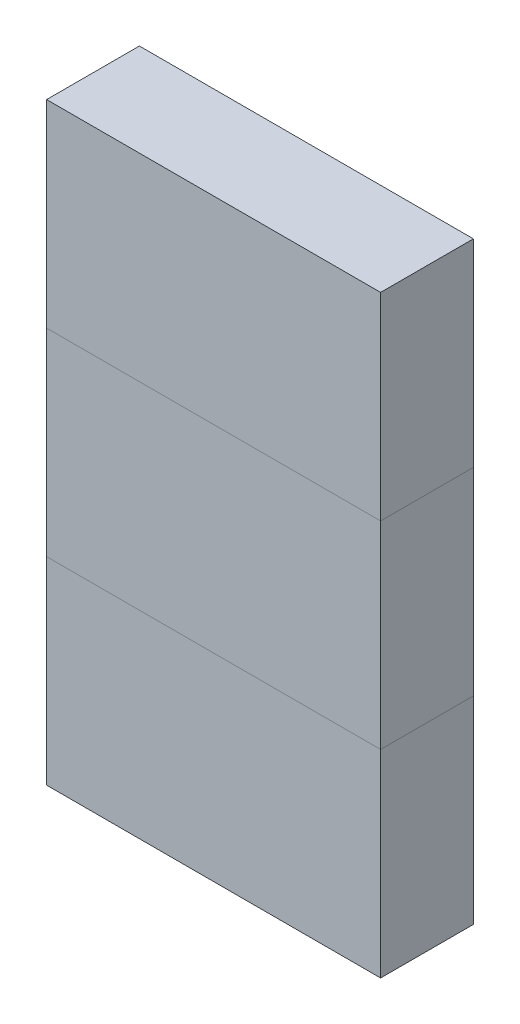
SolidWorks part; units mm, degrees
note: The reader was unsure of these and kept them because the rebuilt part matched: shared geometry of "Sketch2<3>", "Sketch2<4>".
other "middle block"
other "bottom block"
other "top block"
material "ABS"
ref_plane "Front" through (0, 0, 0) normal (0, 0, 1) x (1, 0, 0)
ref_plane "Top" through (0, 0, 0) normal (0, 1, 0) x (1, 0, 0)
ref_plane "Right" through (0, 0, 0) normal (1, 0, 0) x (0, 0, -1)
sketch "Sketch1" plane through (0, 0, 0) normal (0, 1, 0) x (1, 0, 0)
  line L1 (-28.575, 7.9375) -> (28.575, 7.9375)
  line L2 (-28.575, 7.9375) -> (-28.575, -7.9375)
  line L3 (-28.575, -7.9375) -> (28.575, -7.9375)
  line L4 (28.575, 7.9375) -> (28.575, -7.9375)
  line L5 (-28.575, 7.9375) -> (28.575, -7.9375) construction
  line L6 (-28.575, -7.9375) -> (28.575, 7.9375) construction
  point P0 (0, 0)
  dimension "D1" = 15.875
  dimension "D2" = 57.15
extrude "Boss-Extrude1" add sketch "Sketch1" along normal mid plane 101.6
sketch "Sketch2" plane through (0, 0, 0) normal (0, 1, 0) x (1, 0, 0)
  line L1 (-25.4, 1.5875) -> (25.4, 1.5875)
  line L2 (-25.4, 1.5875) -> (-25.4, -1.5875)
  line L3 (-25.4, -1.5875) -> (25.4, -1.5875)
  line L4 (25.4, 1.5875) -> (25.4, -1.5875)
  line L5 (-25.4, 1.5875) -> (25.4, -1.5875) construction
  line L6 (-25.4, -1.5875) -> (25.4, 1.5875) construction
  line L7 (-19.05, 4.7625) -> (19.05, 4.7625)
  line L8 (-19.05, 4.7625) -> (-19.05, -4.7625)
  line L9 (-19.05, -4.7625) -> (19.05, -4.7625)
  line L10 (19.05, 4.7625) -> (19.05, -4.7625)
  line L11 (-19.05, 4.7625) -> (19.05, -4.7625) construction
  line L12 (-19.05, -4.7625) -> (19.05, 4.7625) construction
  point P0 (0, 0)
  point P5 (0, 0)
  dimension "D1" = 50.8
  dimension "D2" = 3.175
  dimension "D3" = 3.175
  dimension "D4" = 38.1
extrude "Cut-Extrude1" cut sketch "Sketch2" against normal offset from surface (47.625 mm away) 3.175 contours L8 L1 L2 L3 | L10 L1 L8 L3 | L10 L7 L8 L1 | L10 L3 L8 L9 | L1 L10 L3 L4 up to face at (0, -50.8, 0)
extrude "Cut-Extrude2" cut sketch "Sketch2<3>" along normal offset from surface (47.625 mm away) 3.175 contours L8 L1 L2 L3 | L10 L1 L8 L3 | L1 L10 L3 L4 up to face at (0, 50.8, 0)
sketch "Sketch2<3>" plane through (0, 0, 0) normal (0, 1, 0) x (1, 0, 0) same geometry as "Sketch2"
extrude "Cut-Extrude3" cut sketch "Sketch2<4>" along normal offset from surface (41.275 mm away) 9.525 contours L10 L3 L8 L9 | L10 L7 L8 L1 up to face at (0, 50.8, 0)
sketch "Sketch2<4>" plane through (0, 0, 0) normal (0, 1, 0) x (1, 0, 0) same geometry as "Sketch2"
sketch "Sketch3" plane through (0, 0, 0) normal (0, 0, 1) x (1, 0, 0)
  line L0 (28.575, 50.8) -> (28.575, 16.9333) construction
  line L1 (28.575, 50.8) -> (28.575, -50.8) construction
  line L2 (28.575, 16.9333) -> (28.575, -16.9333) construction
  line L3 (28.575, -16.9333) -> (28.575, -50.8) construction
  line L4 (28.575, 16.9333) -> (-28.575, 16.9333)
  line L5 (-28.575, 50.8) -> (-28.575, -50.8) construction
  line L6 (28.575, -16.9333) -> (-28.575, -16.9333)
  point P13 (28.575, -16.1004)
split "Split3" trim tools "Sketch3" bodies to split 104 resulting bodies 111 112 113
other "Save Bodies1"
